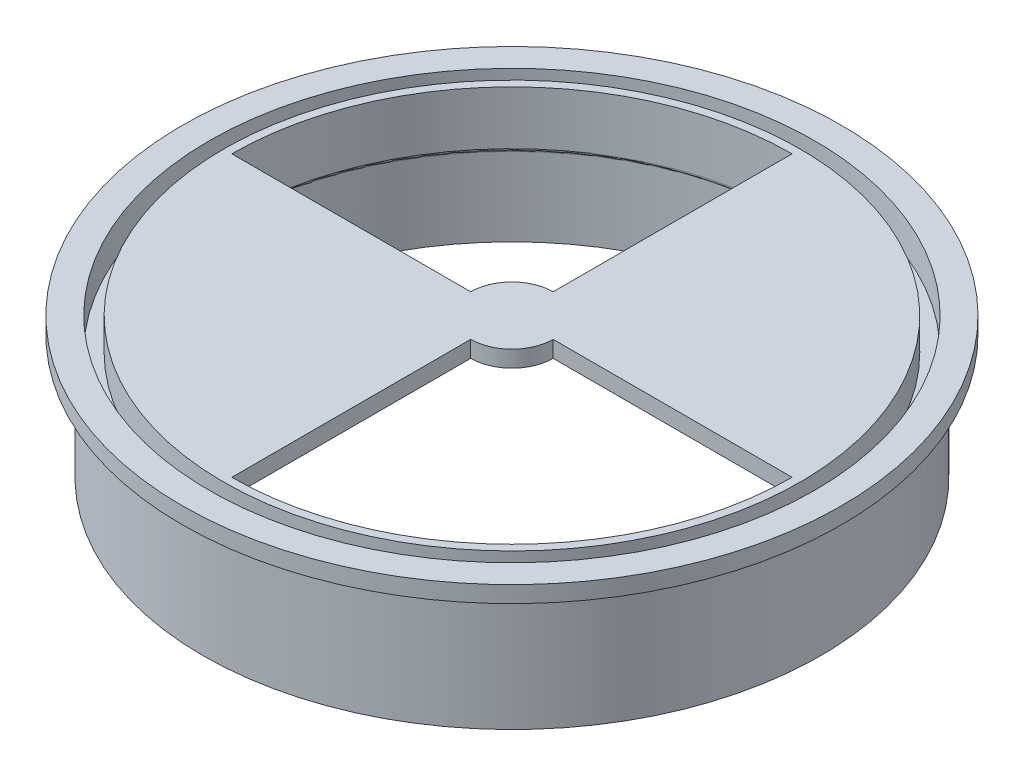
SolidWorks part; units mm, degrees
ref_plane "Alzado" through (0, 0, 0) normal (0, 0, 1) x (1, 0, 0)
ref_plane "Planta" through (0, 0, 0) normal (0, 1, 0) x (1, 0, 0)
ref_plane "Vista lateral" through (0, 0, 0) normal (1, 0, 0) x (0, 0, -1)
sketch "Croquis1" plane through (0, 17, 0) normal (0, 1, 0) x (1, 0, 0)
  circle A3 centre (13.5413, 6.6268) radius 35
  circle A6 centre (13.5413, 6.6268) radius 37.5
extrude "Saliente-Extruir1" add sketch "Croquis1" along normal blind 15
sketch "Croquis2" plane through (0, 32, 0) normal (0, 1, 0) x (1, 0, 0)
  circle A3 centre (13.5413, 6.6268) radius 40
extrude "Saliente-Extruir2" add sketch "Croquis2" along normal blind 2
sketch "Croquis4" plane through (0, 34, 0) normal (0, 1, 0) x (1, 0, 0)
  point P0 (13.5413, 6.6268)
ref_plane "Plano1" through (0, 0, -6.6268) normal (0, 0, 1) x (1, 0, 0)
sketch "Croquis5" plane through (0, 0, -6.6268) normal (0, 0, 1) x (1, 0, 0)
  line L0 (-22.7087, 34.1) -> (-22.7087, 30.1) construction
  line L1 (-22.7087, 30.1) -> (-21.2087, 30.1) construction
  line L2 (-21.2087, 30.1) -> (-22.7087, 34.1) construction
  line L4 (-22.7087, 34.1) -> (-23.2087, 34.1) construction
  line L7 (-26.4587, 33) -> (-23.5712, 33) construction
  line L8 (-23.2087, 34.1) -> (-21.2087, 34.1)
  line L9 (-23.2087, 34.1) -> (-23.2087, 30.1)
  line L10 (-23.2087, 30.1) -> (-21.2087, 30.1)
  line L11 (-21.2087, 34.1) -> (-21.2087, 30.1)
  line L12 (-26.4587, 34) -> (-26.4587, 32) construction
  point P1 (-22.7087, 34.1)
  point P3 (-22.7087, 30.1)
  point P15 (-23.5712, 33)
ref_plane "Plano2" through (0, 33, 0) normal (0, 1, 0) x (1, 0, 0)
sketch "Croquis6" plane through (0, 33, 0) normal (0, 1, 0) x (1, 0, 0)
  circle A0 centre (13.5413, 6.6268) radius 36.25
sketch "Croquis7" plane through (0, 32, 0) normal (0, -1, 0) x (1, 0, 0)
  line L0 (13.5413, -41.6268) -> (13.5413, -11.6268)
  line L1 (48.5413, -6.6268) -> (18.5413, -6.6268)
  line L2 (13.5413, -1.6268) -> (13.5413, 28.3732)
  line L3 (8.5413, -6.6268) -> (-21.4587, -6.6268)
  arc A0 (-21.4587, -6.6268) -> (13.5413, -41.6268) centre (13.5413, -6.6268) ccw
  arc A1 (18.5413, -6.6268) -> (13.5413, -1.6268) centre (13.5413, -6.6268) ccw
  arc A2 (48.5413, -6.6268) -> (13.5413, 28.3732) centre (13.5413, -6.6268) ccw
  arc A3 (8.5413, -6.6268) -> (13.5413, -11.6268) centre (13.5413, -6.6268) ccw
extrude "Cortar-Extruir1" cut sketch "Croquis7" against normal blind 10
sweep "Cortar-Barrer1" cut profiles "Croquis5" path "Croquis6"
sketch "Croquis8" plane through (0, 32, 0) normal (0, -1, 0) x (1, 0, 0)
  circle A0 centre (13.5413, -6.6268) radius 35
  circle A1 centre (13.5413, -6.6268) radius 34
  dimension "D1" = 1
extrude "Saliente-Extruir3" add sketch "Croquis8" against normal up to surface (2 mm away) and the other way blind 5 up to face at (13.5413, 34, 30.1232)
fillet "Redondeo1" radius 0.5 2 edges at (13.5413, 27, -40.6268) (13.5413, 27, -41.6268)
